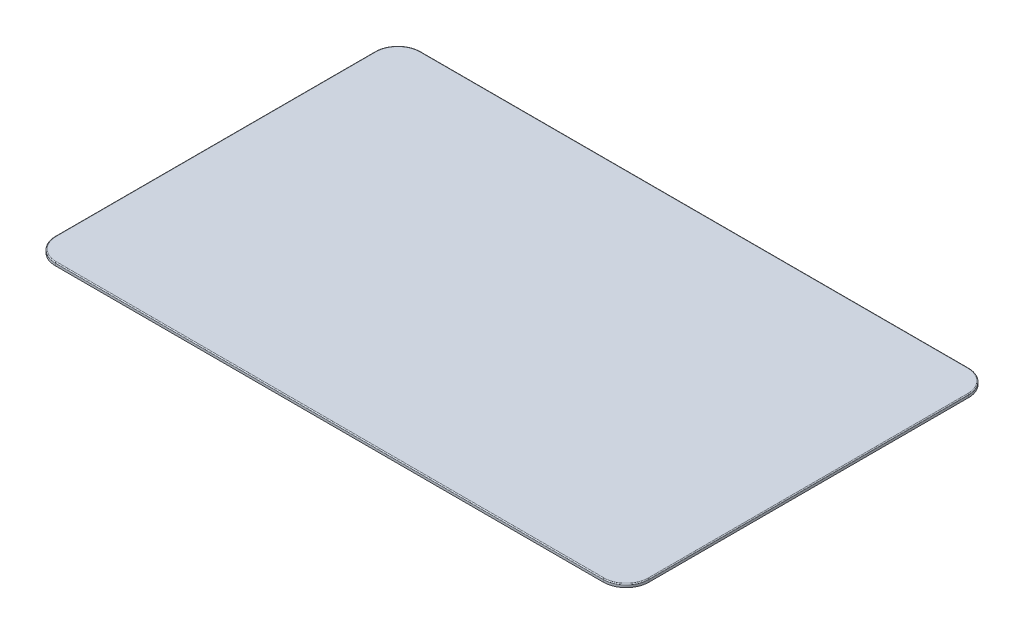
SolidWorks part; units mm, degrees
ref_plane "Спереди" through (0, 0, 0) normal (0, 0, 1) x (1, 0, 0)
ref_plane "Сверху" through (0, 0, 0) normal (0, 1, 0) x (1, 0, 0)
ref_plane "Справа" through (0, 0, 0) normal (1, 0, 0) x (0, 0, -1)
sketch "Эскиз1" plane through (0, 0, 0) normal (0, 1, 0) x (1, 0, 0)
  line L1 (-600, -400) -> (600, -400)
  line L2 (-650, -350) -> (-650, 350)
  line L3 (-600, 400) -> (600, 400)
  line L4 (650, -350) -> (650, 350)
  line L5 (-650, -400) -> (650, 400) construction
  line L6 (-650, 400) -> (650, -400) construction
  arc A0 (-600, 400) -> (-650, 350) centre (-600, 350) ccw
  arc A1 (600, 400) -> (650, 350) centre (600, 350) cw
  arc A2 (650, -350) -> (600, -400) centre (600, -350) cw
  arc A3 (-600, -400) -> (-650, -350) centre (-600, -350) cw
  point P0 (0, 0)
  dimension "D1" = 50
  dimension "D4" = 50
  dimension "D2" = 1300
  dimension "D3" = 800
extrude "Бобышка-Вытянуть1" add sketch "Эскиз1" along normal blind 7
fillet "Скругление1" radius 2 8 edges at (-635.3553, 7, -385.3553) (0, 7, -400) (635.3553, 7, -385.3553) (650, 7, 0) (635.3553, 7, 385.3553) (0, 7, 400) (-635.3553, 7, 385.3553) (-650, 7, 0)
sketch "Эскиз2" plane through (0, 0, 0) normal (0, -1, 0) x (1, 0, 0)
  line L0 (0, 398) -> (0, -400) construction
  line L1 (-240, 283) -> (-190, 283)
  line L2 (-240, 283) -> (-240, 213)
  line L3 (-240, 213) -> (-190, 213)
  line L4 (-190, 283) -> (-190, 213)
  line L5 (-240, 283) -> (-190, 213) construction
  line L6 (-240, 213) -> (-190, 283) construction
  line L7 (250, 398) -> (250, -398) construction
  line L8 (-250, 398) -> (-250, -398) construction
  line L9 (-648, 0) -> (648, 0) construction
  line L15 (-260, 213) -> (-310, 283) construction
  line L16 (-260, 283) -> (-310, 213) construction
  line L17 (-310, 283) -> (-310, 213)
  line L18 (-260, 213) -> (-310, 213)
  line L19 (-260, 283) -> (-260, 213)
  line L20 (-260, 283) -> (-310, 283)
  line L21 (260, 283) -> (260, 213)
  line L22 (240, 283) -> (190, 213) construction
  line L23 (240, 283) -> (240, 213)
  line L24 (310, 283) -> (310, 213)
  line L25 (260, 213) -> (310, 213)
  line L26 (260, 213) -> (310, 283) construction
  line L27 (240, 283) -> (190, 283)
  line L28 (240, 213) -> (190, 283) construction
  line L29 (240, 213) -> (190, 213)
  line L30 (260, 283) -> (310, 283)
  line L31 (190, 283) -> (190, 213)
  line L32 (260, 283) -> (310, 213) construction
  line L33 (260, -283) -> (310, -213) construction
  line L34 (240, -213) -> (190, -283) construction
  line L35 (260, -213) -> (310, -283) construction
  line L36 (240, -283) -> (190, -213) construction
  line L37 (-260, -283) -> (-310, -213) construction
  line L38 (-260, -213) -> (-310, -283) construction
  line L39 (-240, -213) -> (-190, -283) construction
  line L40 (-240, -283) -> (-190, -213) construction
  line L41 (190, -283) -> (190, -213)
  line L42 (260, -283) -> (310, -283)
  line L43 (240, -213) -> (190, -213)
  line L44 (240, -283) -> (190, -283)
  line L45 (260, -213) -> (310, -213)
  line L46 (310, -283) -> (310, -213)
  line L47 (240, -283) -> (240, -213)
  line L48 (260, -283) -> (260, -213)
  line L49 (-260, -283) -> (-310, -283)
  line L50 (-260, -283) -> (-260, -213)
  line L51 (-260, -213) -> (-310, -213)
  line L52 (-310, -283) -> (-310, -213)
  line L53 (-190, -283) -> (-190, -213)
  line L54 (-240, -213) -> (-190, -213)
  line L55 (-240, -283) -> (-240, -213)
  line L56 (-240, -283) -> (-190, -283)
  line L57 (-463, 60) -> (-533, 60)
  line L58 (-463, -10) -> (-533, -60) construction
  line L59 (-463, -60) -> (-533, -60)
  line L60 (-533, -10) -> (-463, -60) construction
  line L61 (-463, 10) -> (-533, 10)
  line L62 (-463, -10) -> (-463, -60)
  line L63 (-533, -10) -> (-533, -60)
  line L64 (-463, 10) -> (-463, 60)
  line L65 (-533, 10) -> (-463, 60) construction
  line L66 (-533, 10) -> (-533, 60)
  line L67 (-463, -10) -> (-533, -10)
  line L68 (-463, 10) -> (-533, 60) construction
  line L69 (463, 10) -> (533, 60) construction
  line L70 (533, 10) -> (463, 60) construction
  line L71 (533, -10) -> (463, -60) construction
  line L72 (463, -10) -> (533, -60) construction
  line L73 (463, -10) -> (533, -10)
  line L74 (533, 10) -> (533, 60)
  line L75 (463, 10) -> (463, 60)
  line L76 (533, -10) -> (533, -60)
  line L77 (463, -10) -> (463, -60)
  line L78 (463, 10) -> (533, 10)
  line L79 (463, -60) -> (533, -60)
  line L80 (463, 60) -> (533, 60)
  line L81 (-25, 35) -> (25, -35) construction
  line L82 (-25, 35) -> (-25, -35)
  line L83 (25, 35) -> (25, -35)
  line L84 (-25, 35) -> (25, 35)
  line L85 (-25, -35) -> (25, -35)
  line L86 (-25, -35) -> (25, 35) construction
  line L87 (35, 35) -> (85, 35)
  line L88 (35, 35) -> (85, -35) construction
  line L89 (35, 35) -> (35, -35)
  line L90 (85, 35) -> (85, -35)
  line L91 (35, -35) -> (85, 35) construction
  line L92 (35, -35) -> (85, -35)
  line L93 (95, 35) -> (145, 35)
  line L94 (95, 35) -> (145, -35) construction
  line L95 (95, 35) -> (95, -35)
  line L96 (145, 35) -> (145, -35)
  line L97 (95, -35) -> (145, 35) construction
  line L98 (95, -35) -> (145, -35)
  line L99 (-85, 35) -> (-35, 35)
  line L100 (-85, 35) -> (-35, -35) construction
  line L101 (-85, 35) -> (-85, -35)
  line L102 (-35, 35) -> (-35, -35)
  line L103 (-85, -35) -> (-35, 35) construction
  line L104 (-85, -35) -> (-35, -35)
  line L105 (-145, 35) -> (-95, 35)
  line L106 (-145, 35) -> (-95, -35) construction
  line L107 (-145, 35) -> (-145, -35)
  line L108 (-95, 35) -> (-95, -35)
  line L109 (-145, -35) -> (-95, 35) construction
  line L110 (-145, -35) -> (-95, -35)
  line L112 (-337.5255, 50) -> (-237.5255, 50)
  line L113 (-337.5255, 50) -> (-337.5255, -50)
  line L114 (-337.5255, -50) -> (-237.5255, -50)
  line L115 (-237.5255, 50) -> (-237.5255, -50)
  line L116 (-337.5255, 50) -> (-237.5255, -50) construction
  line L117 (-337.5255, -50) -> (-237.5255, 50) construction
  point P0 (-215, 248)
  point P14 (-290, 0)
  point P28 (-285, 248)
  point P29 (285, 248)
  point P38 (215, 248)
  point P55 (215, -248)
  point P56 (285, -248)
  point P57 (-285, -248)
  point P58 (-215, -248)
  point P67 (-498, -35)
  point P68 (-498, 35)
  point P77 (498, 35)
  point P78 (498, -35)
  point P79 (0, 0)
  point P84 (60, 0)
  point P89 (120, 0)
  point P94 (-60, 0)
  point P99 (-120, 0)
extrude "Вырез-Вытянуть1" cut sketch "Эскиз2" against normal blind 5
